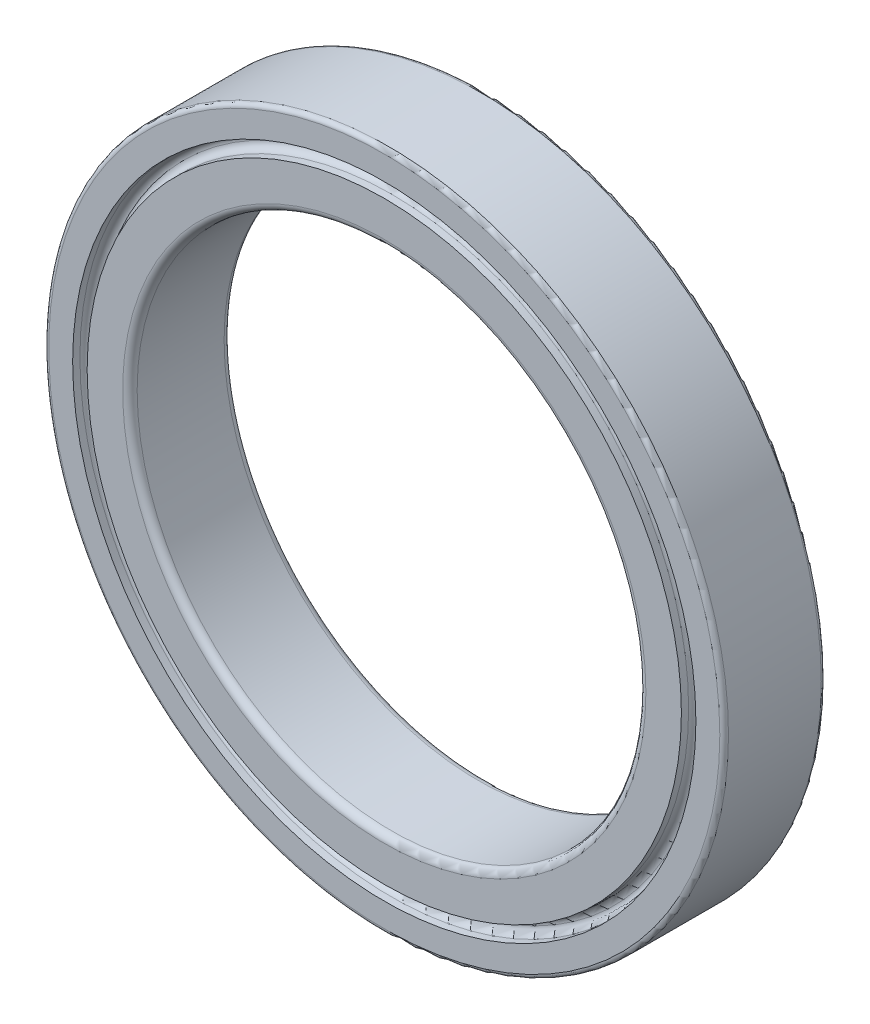
SolidWorks part; units mm, degrees
ref_plane "Front Plane" through (0, 0, 0) normal (0, 0, 1) x (1, 0, 0)
ref_plane "Top Plane" through (0, 0, 0) normal (0, 1, 0) x (1, 0, 0)
ref_plane "Right Plane" through (0, 0, 0) normal (1, 0, 0) x (0, 0, -1)
sketch "Sketch1" plane through (0, 0, 0) normal (0, 0, 1) x (1, 0, 0)
  circle A0 centre (0, 0) radius 23.45
  dimension "D1" = 46.9
extrude "Boss-Extrude1" add sketch "Sketch1" along normal blind 7
sketch "Sketch2" plane through (0, 0, 7) normal (0, 0, 1) x (1, 0, 0)
  circle A0 centre (0, 0) radius 17.55
  dimension "D1" = 35.1
extrude "Cut-Extrude1" cut sketch "Sketch2" against normal through all
fillet "Fillet1" radius 0.5 2 edges at (17.55, 0, 0) (17.55, 0, 7)
sketch "Sketch3" plane through (0, 0, 7) normal (0, 0, 1) x (1, 0, 0)
  circle A0 centre (0, 0) radius 20.5
  circle A1 centre (0, 0) radius 21.5
  dimension "D1" = 41
  dimension "D2" = 1
extrude "Cut-Extrude2" cut sketch "Sketch3" against normal blind 1 contours A1 | A0
fillet "Fillet2" radius 0.5 2 edges at (21.5, 0, 6) (20.5, 0, 6)
fillet "Fillet4" radius 0.3 2 edges at (23.45, 0, 7) (23.45, 0, 0)
sketch "Sketch4" plane through (0, 0, 0) normal (0, 0, -1) x (-1, 0, 0)
  circle A0 centre (0, 0) radius 21
  circle A1 centre (0, 0) radius 22
  dimension "D1" = 42
  dimension "D2" = 1
extrude "Cut-Extrude3" cut sketch "Sketch4" against normal blind 1
fillet "Fillet5" radius 0.5 2 edges at (-22, 0, 1) (-21, 0, 1)
